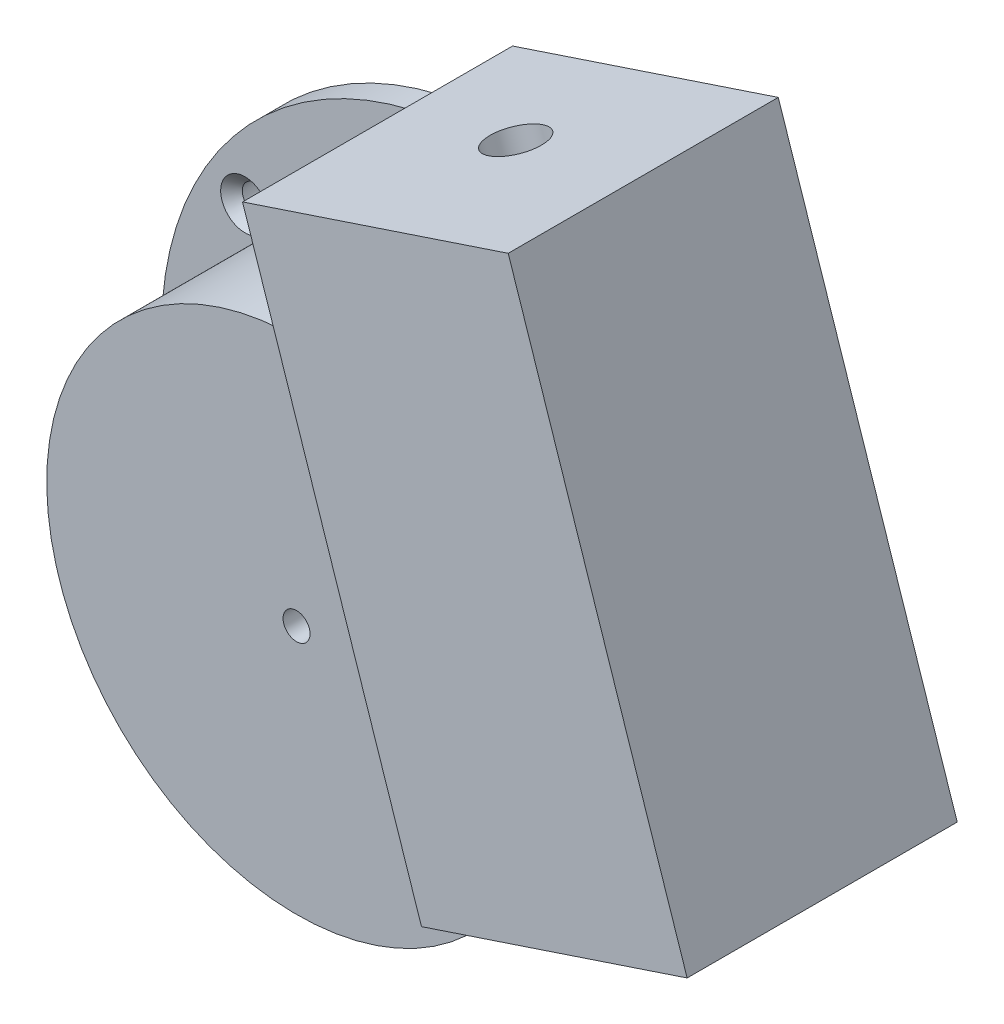
SolidWorks part; units mm, degrees
ref_plane "Piano frontale" through (0, 0, 0) normal (0, 0, 1) x (1, 0, 0)
ref_plane "Piano superiore" through (0, 0, 0) normal (0, 1, 0) x (1, 0, 0)
ref_plane "Piano destro" through (0, 0, 0) normal (1, 0, 0) x (0, 0, -1)
sketch "Schizzo1" plane through (0, 0, 0) normal (0, 0, 1) x (1, 0, 0)
  line L0 (1.7522, 23.936) -> (0, 29.2054)
  line L1 (0, 29.2054) -> (19.6753, 35.7477)
  line L2 (19.6753, 35.7477) -> (32.9272, -4.106)
  line L3 (32.9272, -4.106) -> (22.8076, -7.471)
  line L6 (4.2368, 16.4636) -> (13.2519, -10.6483)
  arc A0 (4.2368, 16.4636) -> (13.2519, -10.6483) centre (0, 0) ccw
  arc A1 (1.7522, 23.936) -> (22.8076, -7.471) centre (0, 0) ccw
  point P3 (15.6548, -6.6278)
  point P9 (12.1261, 24.548)
  point P11 (15.0506, -7.9043)
  point P12 (10.4719, 23.7398)
  point P13 (14.4381, -8.9745)
  point P14 (31.953, -2.7881)
  point P15 (15.6542, -6.6292)
  point P16 (12.8445, 24.063)
  point P17 (16.1482, -5.3137)
  point P18 (29.5605, 27.7151)
  point P19 (32.9692, -4.0585)
  point P20 (12.9536, 25.0369)
  point P21 (34.7279, -6.2084)
  point P22 (15.2372, -7.5384)
  point P23 (12.3243, 25.954)
  point P24 (14.4817, -8.9039)
  point P25 (33.9504, -7.0527)
  point P26 (12.9146, 26.4096)
  point P27 (14.3533, -8.6467)
  point P28 (13.0037, 26.6777)
  point P29 (14.6754, -8.2181)
  point P30 (12.3089, 26.6448)
  point P31 (3.7523, 26.5494)
  point P32 (8.4608, 29.1145)
  point P33 (11.366, -12.6418)
  point P34 (1.2541, 28.4436)
  point P35 (33.2504, -4.8675)
  point P36 (13.2519, -10.6483)
  point P37 (0, 29.2054)
  dimension "D1" = 34
  dimension "D2" = 48
extrude "Estrusione-Estrusione1" add sketch "Schizzo1" along normal blind 2
sketch "Schizzo3" plane through (0, 0, 2) normal (0, 0, 1) x (1, 0, 0)
  line L0 (13.2519, -10.6483) -> (15.6616, -9.8471)
  line L1 (22.8076, -7.471) -> (32.9272, -4.106) construction
  line L2 (4.2368, 16.4636) -> (3.6828, 18.1297)
  line L3 (0, 29.2054) -> (1.7522, 23.936) construction
  arc A1 (3.6828, 18.1297) -> (15.6616, -9.8471) centre (0, 0) ccw
  arc A2 (4.2368, 16.4636) -> (13.2519, -10.6483) centre (0, 0) ccw
  arc A3 (4.2368, 16.4636) -> (13.2519, -10.6483) centre (0, 0) ccw construction
  dimension "D1" = 37
extrude "Estrusione-Estrusione3" add sketch "Schizzo3" along normal blind 12
sketch "Schizzo5" plane through (0, 0, 2) normal (0, 0, 1) x (1, 0, 0)
  line L0 (4.2368, 16.4636) -> (9.2007, 7.8737)
  line L1 (9.2007, 7.8737) -> (2.5289, 27.9386)
  line L2 (2.5289, 27.9386) -> (18.4085, 33.2188)
  line L3 (18.4085, 33.2188) -> (30.3983, -2.8392)
  line L4 (30.3983, -2.8392) -> (12.6208, -8.7505)
  line L5 (13.2519, -10.6483) -> (12.6208, -8.7505)
  line L6 (13.2519, -10.6483) -> (32.9272, -4.106)
  line L7 (32.9272, -4.106) -> (19.6753, 35.7477)
  line L8 (19.6753, 35.7477) -> (0, 29.2054)
  line L9 (0, 29.2054) -> (4.2368, 16.4636)
  line L10 (13.2519, -10.6483) -> (4.2368, 16.4636) construction
  dimension "D1" = 2
  dimension "D2" = 2
  dimension "D3" = 2
  dimension "D4" = 2
extrude "Estrusione-Estrusione4" add sketch "Schizzo5" along normal blind 12
sketch "Schizzo7" plane through (0, 0, 2) normal (0, 0, 1) x (1, 0, 0)
  circle A0 centre (0, 0) radius 17
extrude "Taglio-Estrusione1" cut sketch "Schizzo7" against normal mid plane 24
sketch "Schizzo10" plane through (0, 0, 14) normal (0, 0, 1) x (1, 0, 0)
  line L0 (18.4085, 33.2188) -> (30.3983, -2.8392) construction
  line L1 (30.3983, -2.8392) -> (14.5187, -8.1194)
  line L2 (30.3983, -2.8392) -> (18.4085, 33.2188)
  line L3 (18.4085, 33.2188) -> (2.5289, 27.9386)
  line L4 (14.5187, -8.1194) -> (2.5289, 27.9386)
  line L5 (32.9272, -4.106) -> (13.2519, -10.6483)
  line L6 (32.9272, -4.106) -> (19.6753, 35.7477)
  line L7 (19.6753, 35.7477) -> (0, 29.2054)
  line L8 (13.2519, -10.6483) -> (0, 29.2054)
extrude "Estrusione-Estrusione5" add sketch "Schizzo10" along normal blind 4
sketch "Schizzo11" plane through (0, 0, 18) normal (0, 0, 1) x (1, 0, 0)
  line L0 (13.2519, -10.6483) -> (15.6616, -9.8471) construction
  line L1 (32.9272, -4.106) -> (13.2519, -10.6483)
  line L2 (32.9272, -4.106) -> (19.6753, 35.7477)
  line L3 (19.6753, 35.7477) -> (0, 29.2054)
  line L4 (13.2519, -10.6483) -> (0, 29.2054)
  arc A0 (4.2368, 16.4636) -> (13.2519, -10.6483) centre (0, 0) ccw construction
extrude "Estrusione-Estrusione6" add sketch "Schizzo11" along normal blind 2
sketch "Schizzo12" plane through (0, 0, 14) normal (0, 0, 1) x (1, 0, 0)
  circle A0 centre (0, 0) radius 18.5
extrude "Estrusione-Estrusione7" add sketch "Schizzo12" along normal blind 2
sketch "Schizzo13" plane through (0, 0, 16) normal (0, 0, 1) x (1, 0, 0)
  circle A0 centre (0, 0) radius 1
  dimension "D1" = 2
extrude "Taglio-Estrusione2" cut sketch "Schizzo13" against normal blind 2
sketch "Schizzo14" plane through (-8.7444, 26.2978, 0) normal (-0.3155, 0.9489, 0) x (0.9489, 0.3155, 0)
  line L0 (9.2151, -16) -> (9.2151, -18) construction
  line L1 (9.2151, -20) -> (9.2151, 0) construction
  line L2 (9.2151, -18) -> (28.6731, 0) construction
  line L3 (29.9496, 0) -> (9.2151, 0) construction
  line L5 (9.2151, 0) -> (29.9496, -18) construction
  line L6 (29.9496, -20) -> (29.9496, 0) construction
  circle A0 centre (18.9441, -9) radius 2
  dimension "D2" = 4
  dimension "D1" = 2
extrude "Taglio-Estrusione3" cut sketch "Schizzo14" against normal blind 2
sketch "Schizzo15" plane through (0, 0, 2) normal (0, 0, 1) x (1, 0, 0)
  line L0 (12.7002, 20.3643) -> (-12.7002, -20.3643) construction
  line L1 (-20.3643, 12.7002) -> (20.3643, -12.7002) construction
  line L2 (0, 0) -> (0.8165, 23.9861) construction
  circle A0 centre (0, 0) radius 21
  arc A1 (1.7522, 23.936) -> (22.8076, -7.471) centre (0, 0) ccw construction
  dimension "D3" = 30
  dimension "D1" = 42
  dimension "D2" = 24
hole_wizard "Foro svasato per Vite M1.6-1" positions "Schizzo3D1" profile "Schizzo16" countersink size "M1.6" standard "ISO" end condition through all
sketch3d "Schizzo3D1"
  line L0 (0, 0, 2) -> (0.8165, 23.9861, 2) construction
  line L1 (-20.3643, 12.7002, 2) -> (20.3643, -12.7002, 2) construction
  line L2 (12.7002, 20.3643, 2) -> (-12.7002, -20.3643, 2) construction
  circle A0 centre (0, 0, 2) radius 21 construction
  point P0 (0.7144, 20.9878, 2)
  point P6 (0, 0, 23)
  point P7 (-17.8188, 11.1126, 2)
  point P11 (-11.1126, -17.8188, 2)
  point P15 (17.8188, -11.1126, 2)
sketch "Schizzo16" plane through (0.7144, 20.9878, 2) normal (1, 0, 0) x (0, -1, 0)
  line L0 (0, 0) -> (0, 2)
  line L1 (0, 2) -> (1, 2)
  line L2 (1, 2) -> (1, 0.8)
  line L3 (1, 0.8) -> (1.8, 0)
  line L5 (1.8, 0) -> (0, 0)
  line L6 (-1, 0.8) -> (-1.8, 0) construction
  line L11 (0, -6.35) -> (0, 107.95) construction
  dimension "Thru Hole Dia." = 2
  dimension "Thru Hole Depth" = 2
  dimension "Near C'Sink Dia." = 3.6
  dimension "Near C'Sink Angle" = 90
